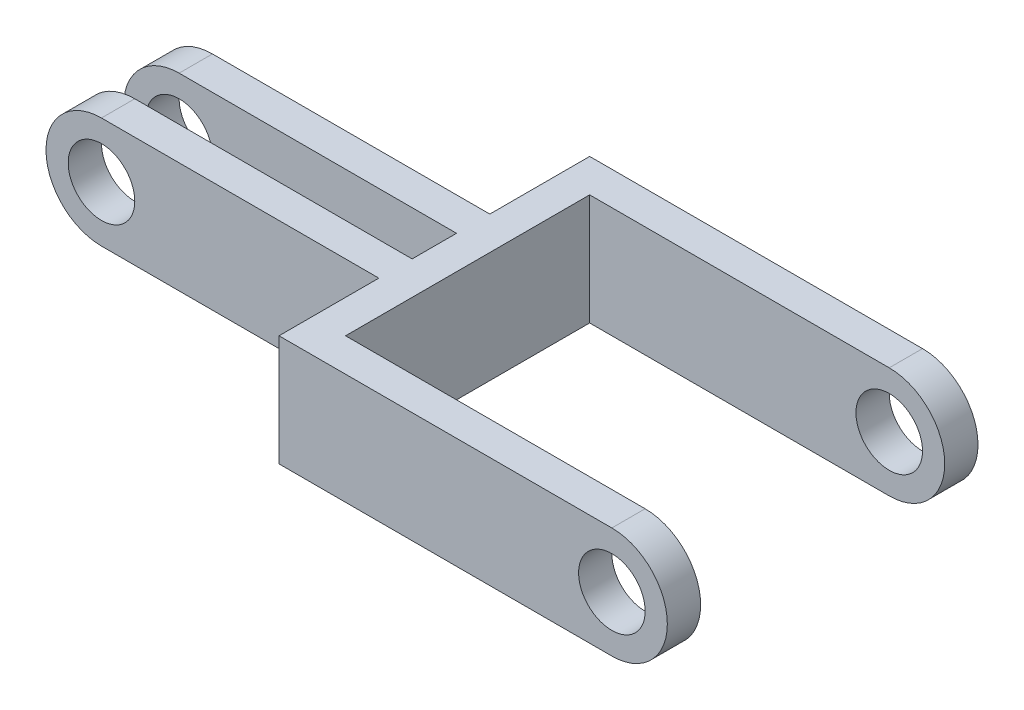
SolidWorks part; units mm, degrees
ref_plane "Front Plane" through (0, 0, 0) normal (0, 0, 1) x (1, 0, 0)
ref_plane "Top Plane" through (0, 0, 0) normal (0, 1, 0) x (1, 0, 0)
ref_plane "Right Plane" through (0, 0, 0) normal (1, 0, 0) x (0, 0, -1)
sketch "Sketch1" plane through (0, 0, 0) normal (0, 0, 1) x (1, 0, 0)
  line L0 (12.5, 10) -> (12.5, 0) construction
  line L1 (0, 0) -> (25, 0)
  line L3 (0, 10) -> (25, 10)
  line L4 (25, 10) -> (25, 0)
  arc A0 (0, 10) -> (0, 0) centre (0, 5) ccw
  circle A2 centre (0, 5) radius 3
  dimension "D3" = 6
  dimension "D1" = 10
  dimension "D2" = 25
extrude "Boss-Extrude1" add sketch "Sketch1" along normal blind 3
sketch "Sketch2" plane through (25, 0, 0) normal (1, 0, 0) x (0, 0, -1)
  line L1 (-3, 0) -> (6, 0)
  line L2 (-3, 0) -> (-3, 10)
  line L3 (-3, 10) -> (6, 10)
  line L4 (6, 0) -> (6, 10)
  dimension "D1" = 9
  dimension "D2" = 10
extrude "Boss-Extrude2" add sketch "Sketch2" along normal blind 3
sketch "Sketch3" plane through (0, 0, -6) normal (0, 0, -1) x (-1, 0, 0)
  line L0 (-28, 10) -> (-25, 10) construction
  line L1 (-25, 0) -> (-55, 0)
  line L2 (-25, 0) -> (-25, 10)
  line L3 (-25, 10) -> (-55, 10)
  line L4 (-55, 0) -> (-55, 10)
  dimension "D1" = 30
extrude "Boss-Extrude3" add sketch "Sketch3" along normal blind 3
ref_plane "Plane1" through (0, 0, 1.5) normal (0, 0, -1) x (-1, 0, 0)
sketch "Sketch5" plane through (0, 0, -9) normal (0, 0, -1) x (-1, 0, 0)
  line L0 (-55, 10) -> (-55, 0)
  arc A0 (-55, 10) -> (-55, 0) centre (-55, 5) ccw
extrude "Boss-Extrude4" add sketch "Sketch5" against normal up to surface (3 mm away) up to face at (41.5, 5, -6)
sketch "Sketch6" plane through (0, 0, -9) normal (0, 0, -1) x (-1, 0, 0)
  circle A0 centre (-55, 5) radius 3
  dimension "D1" = 6
extrude "Cut-Extrude1" cut sketch "Sketch6" against normal blind 3
ref_plane "Plane2" through (0, 0, 5) normal (0, 0, 1) x (1, 0, 0)
sketch "Sketch7" plane through (0, 10, 0) normal (0, 1, 0) x (1, 0, 0)
  line L1 (28, -3) -> (25, -3)
  line L2 (28, -3) -> (28, -11)
  line L3 (28, -11) -> (25, -11)
  line L4 (25, -3) -> (25, -11)
  dimension "D1" = 8
  dimension "D2" = 3
extrude "Boss-Extrude5" add sketch "Sketch7" against normal up to surface (10 mm away) up to face at (27, 0, -3)
mirror "Mirror5" about plane through (0, 0, 5) normal (0, 0, 1) of "Cut-Extrude1", "Boss-Extrude1", "Boss-Extrude3", "Boss-Extrude4", "Boss-Extrude2", "Boss-Extrude5"
ref_axis "Axis1" through (55, 5, 20.3377) along (0, 0, -1)
ref_axis "Axis2" through (0, 5, 0.0769) along (0, 0, 1)
